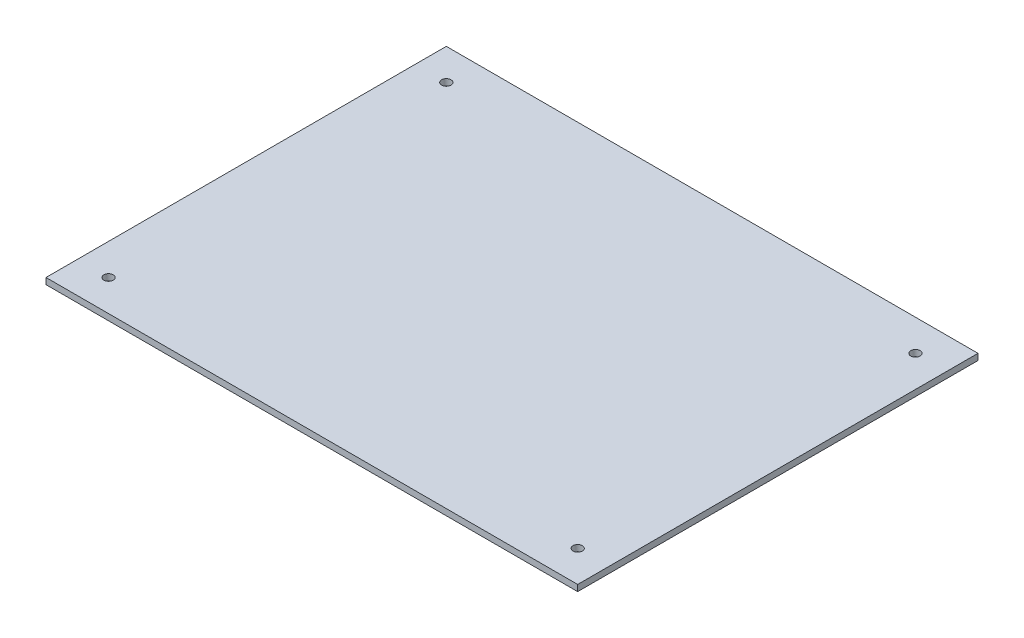
SolidWorks part; units mm, degrees
ref_plane "Спереди" through (0, 0, 0) normal (0, 0, 1) x (1, 0, 0)
ref_plane "Сверху" through (0, 0, 0) normal (0, 1, 0) x (1, 0, 0)
ref_plane "Справа" through (0, 0, 0) normal (1, 0, 0) x (0, 0, -1)
sketch "Эскиз1" plane through (0, 0, 0) normal (0, 1, 0) x (1, 0, 0)
  line L0 (10.6415, 53.6415) -> (10.6415, -74.3585) construction
  line L1 (-74.3585, 53.6415) -> (95.6415, 53.6415)
  line L2 (-74.3585, 53.6415) -> (-74.3585, -74.3585)
  line L3 (-74.3585, -74.3585) -> (95.6415, -74.3585)
  line L4 (95.6415, 53.6415) -> (95.6415, -74.3585)
  line L5 (-74.3585, -10.3585) -> (95.6415, -10.3585) construction
  circle A0 centre (-64.3585, 43.6415) radius 1.5
  circle A1 centre (85.6415, 43.6415) radius 1.5
  circle A2 centre (85.6415, -64.3585) radius 1.5
  circle A3 centre (-64.3585, -64.3585) radius 1.5
  point P0 (0, 0)
  point P12 (10.6415, -10.3585)
  dimension "D1" = 10
  dimension "D2" = 10
  dimension "D3" = 128
  dimension "D4" = 170
extrude "Бобышка-Вытянуть1" add sketch "Эскиз1" along normal blind 2
